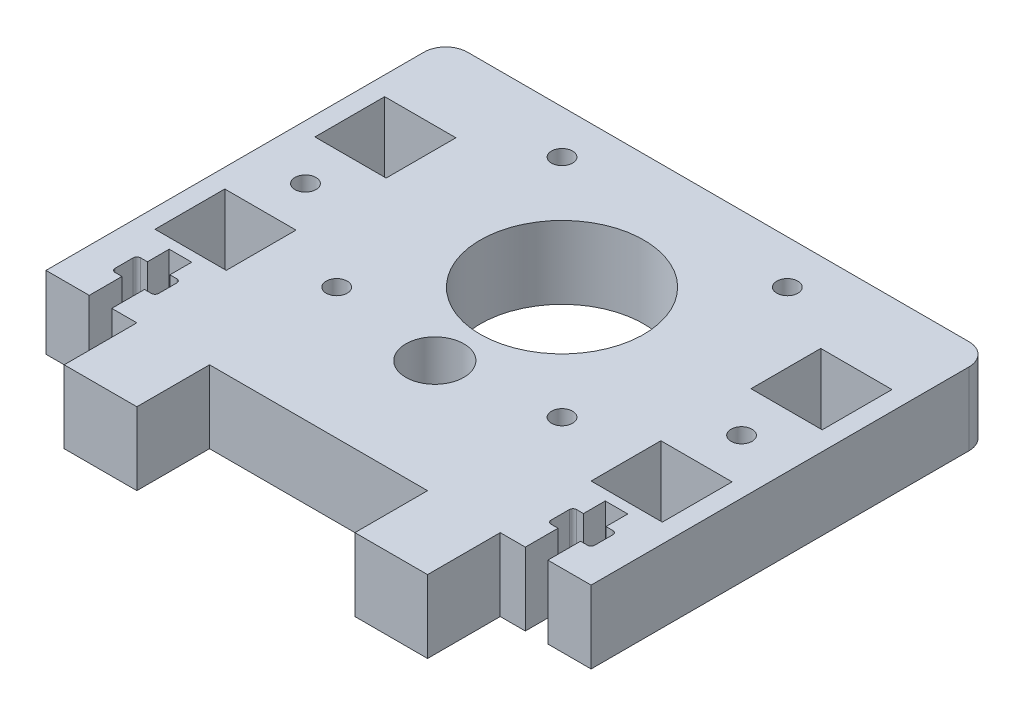
SolidWorks part; units mm, degrees
ref_plane "Front Plane" through (0, 0, 0) normal (0, 0, 1) x (1, 0, 0)
ref_plane "Top Plane" through (0, 0, 0) normal (0, 1, 0) x (1, 0, 0)
ref_plane "Right Plane" through (0, 0, 0) normal (1, 0, 0) x (0, 0, -1)
sketch "Sketch1" plane through (0, 0, 0) normal (0, 1, 0) x (1, 0, 0)
  line L0 (0, 29) -> (0, -6) construction
  line L1 (-34.5, 29) -> (0, 29)
  line L2 (-37.5, 26) -> (-37.5, -26)
  line L3 (-37.5, -26) -> (-25, -26)
  line L4 (0, 29) -> (0, 18.75)
  line L5 (0, -3.75) -> (0, -6)
  line L6 (0, -14) -> (0, -26) construction
  line L7 (-11.25, 7.5) -> (0, 7.5) construction
  line L8 (0, -14) -> (0, -26)
  line L9 (-30, 18) -> (-30, 8.4) construction
  line L10 (-37.5, 2.2) -> (0, 2.2) construction
  line L11 (-34.9, 18) -> (-25.1, 18)
  line L12 (-34.9, 18) -> (-34.9, 8.4)
  line L13 (-34.9, 8.4) -> (-25.1, 8.4)
  line L14 (-25.1, 18) -> (-25.1, 8.4)
  line L15 (-34.9, 18) -> (-25.1, 8.4) construction
  line L16 (-34.9, 8.4) -> (-25.1, 18) construction
  line L17 (-34.9, -4) -> (-25.1, -13.6) construction
  line L18 (-34.9, -13.6) -> (-25.1, -4) construction
  line L19 (-25.1, -13.6) -> (-25.1, -4)
  line L20 (-34.9, -4) -> (-25.1, -4)
  line L21 (-34.9, -13.6) -> (-34.9, -4)
  line L22 (-34.9, -13.6) -> (-25.1, -13.6)
  line L23 (-30, -4) -> (-30, -13.6) construction
  line L24 (-30, -8.8) -> (-30, 13.2) construction
  line L25 (0, 7.5) -> (-15.5, 23) construction
  line L35 (-15, -26) -> (0, -26)
  line L43 (-20, -36) -> (-20, -24.6) construction
  line L44 (-15, -26) -> (-15, -36)
  line L45 (-15, -36) -> (-25, -36)
  line L46 (-25, -36) -> (-25, -26)
  arc A1 (-34.5, 29) -> (-37.5, 26) centre (-34.5, 26) ccw
  arc A2 (0, 18.75) -> (0, -3.75) centre (0, 7.5) ccw
  circle A4 centre (-15.5, 23) radius 1.45
  circle A6 centre (-15.5, -8) radius 1.45
  circle A7 centre (-30, 2.2) radius 1.45
  arc A10 (0, -6) -> (0, -14) centre (0, -10) ccw
  point P0 (0, 0)
  point P28 (-30, 13.2)
  point P39 (-30, -8.8)
  dimension "D7" = 22.5
  dimension "D17" = 8
  dimension "D14" = 2.9
  dimension "D6" = 3
  dimension "D19" = 2.9
  dimension "D1" = 55
  dimension "D9" = 9.8
  dimension "D10" = 9.6
  dimension "D22" = 10
  dimension "D23" = 10
  dimension "D16" = 17.5
  dimension "D11" = 22
  dimension "D13" = 2.2
  dimension "D3" = 37.5
  dimension "D4" = 31
  dimension "D5" = 15.5
  dimension "D15" = 26
  dimension "D18" = 37.5
  dimension "D20" = 20
  dimension "D8" = 16
  dimension "D12" = 30
extrude "MainLayout" add sketch "Sketch1" along normal blind 10
sketch "Sketch2" plane through (0, 10, 0) normal (0, 1, 0) x (1, 0, 0)
  line L0 (-30, -26) -> (-30, -15) construction
  line L1 (-28.45, -21.5) -> (-28.45, -26)
  line L2 (-37.5, -26) -> (-25, -26) construction
  line L3 (-28.45, -15) -> (-31.55, -15)
  line L4 (-31.55, -15) -> (-31.55, -18)
  line L5 (-31.55, -18) -> (-32.5, -18)
  line L6 (-33, -18.5) -> (-33, -21)
  line L7 (-32.5, -21.5) -> (-31.55, -21.5)
  line L8 (-31.55, -21.5) -> (-31.55, -26)
  line L9 (-31.55, -26) -> (-28.45, -26)
  line L10 (-27.5, -21.5) -> (-28.45, -21.5)
  line L11 (-27, -18.5) -> (-27, -21)
  line L12 (-28.45, -18) -> (-27.5, -18)
  line L13 (-28.45, -15) -> (-28.45, -18)
  line L14 (0, -26) -> (0, -14) construction
  line L30 (-30, -26) -> (-30, -15) construction
  arc A0 (-27, -18.5) -> (-27.5, -18) centre (-27.5, -18.5) ccw
  arc A1 (-32.5, -18) -> (-33, -18.5) centre (-32.5, -18.5) ccw
  arc A2 (-27.5, -21.5) -> (-27, -21) centre (-27.5, -21) ccw
  arc A3 (-33, -21) -> (-32.5, -21.5) centre (-32.5, -21) ccw
  point P17 (0, -20)
  point P38 (-27, -18)
  point P41 (-33, -18)
  point P44 (-27, -21.5)
  point P47 (-33, -21.5)
  dimension "D8" = 0.5
  dimension "D1" = 1.55
  dimension "D2" = 0
  dimension "D3" = 3.5
  dimension "D5" = 11
  dimension "D6" = 3
  dimension "D4" = 8
  dimension "D7" = 30
extrude "TSlot" cut sketch "Sketch2" against normal through all
mirror "Mirror1" about plane through (0, 0, 0) normal (1, 0, 0) of "TSlot", "MainLayout"
equation "\"Y-ROD-SPACING\"=75"
equation "\"Y-BED-OFFSET\"=2"
equation "\"Y-BED-ROD-INSET\"=3.5"
equation "\"T-SLOT-NUT-FILLET-RADIUS\"=0.5"
equation "\"T-SLOT-SCREW-SHAFT-RADIUS\"=1.55"
equation "\"T-SLOT-SCREW-SHAFT-CUTOUT-LENGTH\"=11.0"
equation "\"T-SLOT-NUT-DEPTH\"=3.5"
equation "\"T-SLOT-NUT-WIDTH\"=2.85"
equation "\"T-SLOT-NUT-END-DISTANCE\"=8"
equation "\"ACRYLIC-TAB-CUTOUT-SIZE\"=\"ACRYLIC-THICKNESS\"+\"ACRYLIC-TAB-TOLERANCE\"*2"
equation "\"ACRYLIC-TAB-WIDTH\"=\"ACRYLIC-THICKNESS\""
equation "\"ACRYLIC-M3-HOLE\"=2.9"
equation "\"SMOOTHROD-CAP-SCREW-DISTANCE\"=20"
equation "\"FRAME-WIDTH-INNER\"=370"
equation "\"NEMA17-HOLE-SPACING\"=31"
equation "\"NEMA17-CENTRAL-CUTOUT\"=22.5"
equation "\"D7@Sketch1\"=\"NEMA17-CENTRAL-CUTOUT\""
equation "\"D5@Sketch1\"=\"NEMA17-HOLE-SPACING\"/2"
equation "\"D4@Sketch1\"=\"NEMA17-HOLE-SPACING\""
equation "\"D19@Sketch1\"=\"ACRYLIC-M3-HOLE\""
equation "\"D14@Sketch1\"=\"ACRYLIC-M3-HOLE\""
equation "\"D9@Sketch1\"=\"ACRYLIC-THICKNESS\"-\"KERF\"*2"
equation "\"D10@Sketch1\"=\"ACRYLIC-TAB-WIDTH\"-\"KERF\"*4"
equation "\"D23@Sketch1\"=\"ACRYLIC-TAB-WIDTH\""
equation "\"D22@Sketch1\"=\"ACRYLIC-TAB-WIDTH\""
equation "\"D5@Sketch2\"=\"T-SLOT-SCREW-SHAFT-CUTOUT-LENGTH\""
equation "\"D4@Sketch2\"=\"T-SLOT-NUT-END-DISTANCE\""
equation "\"D3@Sketch2\"=\"T-SLOT-NUT-DEPTH\""
equation "\"D1@Sketch2\"=\"T-SLOT-SCREW-SHAFT-RADIUS\""
equation "\"D8@Sketch2\"=\"T-SLOT-NUT-FILLET-RADIUS\""
equation "\"Z-BRACKET-REACH\"=55"
equation "\"D1@Sketch1\"=\"Z-BRACKET-REACH\""
equation "\"Z-ROD-SPACING\"=17.5"
equation "\"ACRYLIC-THICKNESS\"=10"
equation "\"TOP-BRACKET-SPACING\"=40"
equation "\"SMOOTHROD-X-LENGTH\"=350"
equation "\"SMOOTHROD-Y-LENGTH\"=350"
equation "\"SMOOTHROD-Z-LENGTH\"=350"
equation "\"SMOOTHROD-TIGHTENING-HEADROOM\"=.25"
equation "\"LEADSCREW-Z-LENGTH\"=300"
equation "\"D16@Sketch1\"=\"Z-ROD-SPACING\""
equation "\"X-ROD-SPACING\"=45"
equation "\"ACRYLIC-THICKNESS2\"=4.5"
equation "\"SCREW-LENGTH-FRAME\"=\"ACRYLIC-THICKNESS\" + 10"
equation "\"SCREW-HEAD-RADIUS\"=6"
equation "\"PRINTED-X-SMOOTHROD-DIAMETER\"=9.0"
equation "\"PRINTED-X-SMOOTHROD-CUTOUT\"=10"
equation "\"PRINTED-X-BASE-HEIGHT\"=10"
equation "\"PRINTED-LM8UU-CUTOUT-SIZE\"=15.5"
equation "\"PRINTED-LM8UU-CUTOUT-LENGTH\"=24.5"
equation "\"PRINTED-X-IDLER-HEIGHT\"=16"
equation "\"PSU-MOUNTING-WIDTH\"=95"
equation "\"PSU-MOUNTING-HEIGHT\"=177"
equation "\"D1@MainLayout\"=\"ACRYLIC-THICKNESS\""
equation "\"Z-ROD-INSET\"=16"
equation "\"Y-BELT-TO-ROD-DISTANCE\"=20"
equation "\"SPOOL-HOLDER-ROD-SPACING\"=150"
equation "\"D8@Sketch1\"=\"Z-ROD-INSET\""
equation "\"Y-BED-SCREW-SPACING\"=209"
equation "\"Y-BED-SCREW-CUTOUT-SLOT-HEIGHT\"=2"
equation "\"ACRYLIC-TAB-TOLERANCE\"=-.05"
equation "\"SCREW-LENGTH-MOTOR\"=\"ACRYLIC-THICKNESS\" + 5"
equation "\"SCREW-LENGTH-EXTRUDER\"=28"
equation "\"ACRYLIC-X-CARRIAGE-WIDTH\"=55"
equation "\"ACRYLIC-X-CARRIAGE-HEIGHT\"=75"
equation "\"ACRYLIC-X-CARRIAGE-LM8UU-CUTOUT-WIDTH\"=24.25"
equation "\"ACRYLIC-X-CARRIAGE-SCREW-SPACING-X\"=15"
equation "\"ACRYLIC-X-CARRIAGE-SCREW-SPACING-Y\"=33"
equation "\"ACRYLIC-X-CARRIAGE-CENTER-TAB-SPACING\"=14"
equation "\"ACRYLIC-X-CARRIAGE-EXTRUDER-OFFSET\"=26"
equation "\"ACRYLIC-X-CARRIAGE-EXTRUDER-ANGLE\"=90"
equation "\"ACRYLIC-X-CARRIAGE-EXTRUDER-SHELF-DEPTH\"=\"ACRYLIC-X-CARRIAGE-EXTRUDER-OFFSET\" + 28"
equation "\"ACRYLIC-X-CARRIAGE-EXTRUDER-BRACE-SPACING\"=23"
equation "\"ACRYLIC-X-CARRIAGE-EXTRUDER-BRACE-TAB-OFFSET\"=20"
equation "\"ACRYLIC-X-CARRIAGE-EXTRUDER-BRACE-HEIGHT\"=35"
equation "\"ACRYLIC-X-CARRIAGE-EXTRUDER-BRACE-SCREW-SPACING\"=22"
equation "\"KERF\"=0.1"
equation "\"PRINTED-M3-HOLE\"=3.5"
equation "\"PRINTED-M3-NUT-AF\"=6.25"
equation "\"ACRYLIC-X-CARRIAGE-LM8UU-CUTOUT-HEIGHT\"=11.0"
equation "\"ACRYLIC-X-CARRIAGE-DUAL-WIDTH-MULTIPLIER\"=1.65"
equation "\"ACRYLIC-X-CARRIAGE-DUAL-HOTEND-SPACING\"=42"
equation "\"ACRYLIC-X-CARRIAGE-DUAL-WIDTH\"=75"
equation "\"ACRYLIC-X-CARRIAGE-DUAL-FAN-OFFSET\"=52"
equation "\"ACRYLIC-X-CARRIAGE-DUAL-FAN-HEIGHT\"=20"
equation "\"ACRYLIC-X-CARRIAGE-DUAL-HOTEND-SEPARATION\"=36"
equation "\"ACRYLIC-X-CARRIAGE-DUAL-MOUNT-PLATE-DEPTH\"=75"
equation "\"ACRYLIC-X-CARRIAGE-DUAL-MOUNT-BRACE-WIDTH\"=33"
equation "\"ACRYLIC-X-CARRIAGE-DUAL-MOUNT-SCREW-WIDTH\"=40"
equation "\"BLOWER-FAN-WIDTH\"=15"
